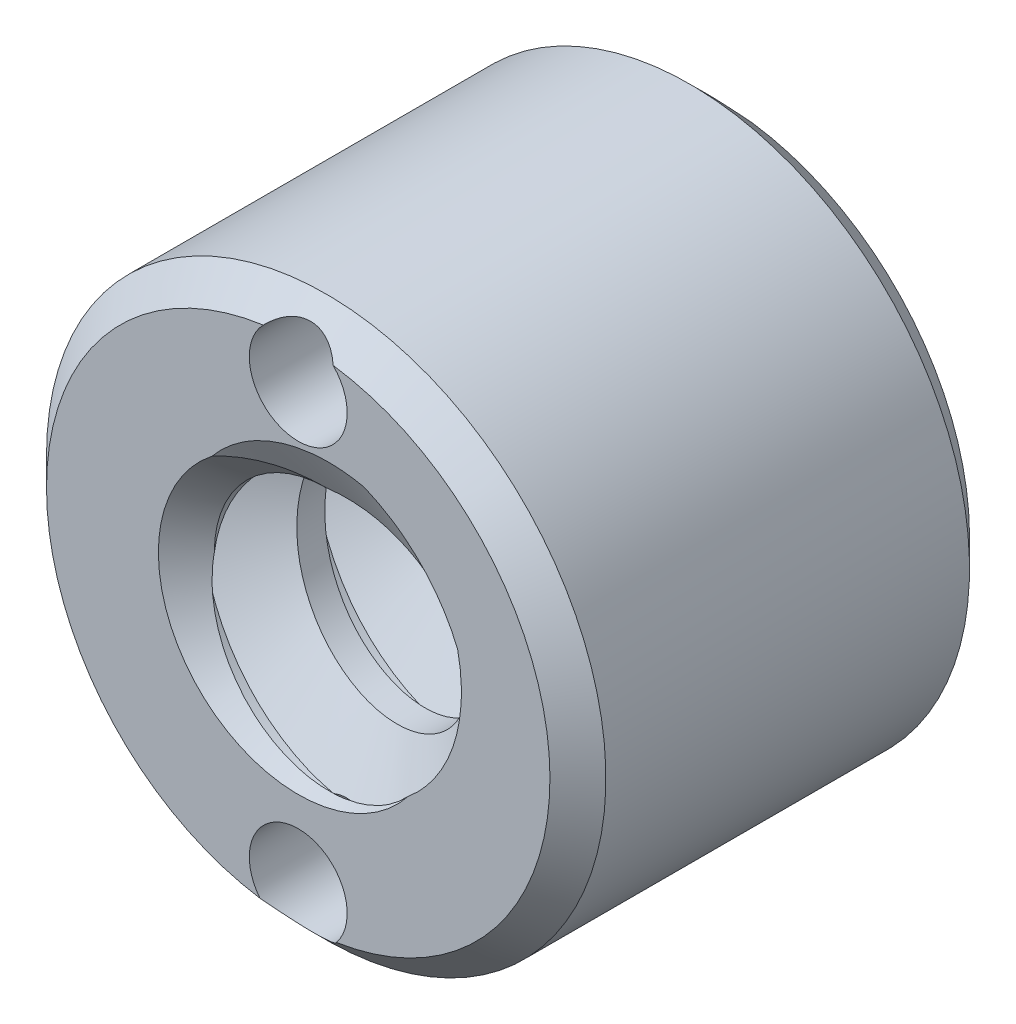
SolidWorks part; units mm, degrees
material "Alliage 1060"
ref_plane "Front Plane" through (0, 0, 0) normal (0, 0, 1) x (1, 0, 0)
ref_plane "Top Plane" through (0, 0, 0) normal (0, 1, 0) x (1, 0, 0)
ref_plane "Right Plane" through (0, 0, 0) normal (1, 0, 0) x (0, 0, -1)
sketch "Sketch1" plane through (0, 0, 0) normal (0, 0, 1) x (1, 0, 0)
  circle A0 centre (0, 0) radius 4
  circle A1 centre (0, 0) radius 10
  circle A2 centre (0, 7.6883) radius 1.75
  circle A3 centre (0, -7.805) radius 1.75
  dimension "D1" = 20
  dimension "D2" = 8
  dimension "D3" = 3.5
extrude "Boss-Extrude1" add sketch "Sketch1" along normal blind 15
chamfer "Chamfer3" distance 1 angle 45 4 edges at (4, 0, 15) (4, 0, 0) (10, 0, 0) (10, 0, 15)
thread "Thread1" pitch 4 method cut profile "Thread Profile1" start angle 0, offset 4, length 0, pitch 4, diameter 8
ref_plane "Plane1" through (-4, 0, 18) normal (0, -1, 0) x (-1, 0, 0)
sketch "Thread Profile1" plane through (-4, 0, 18) normal (0, -1, 0) x (-1, 0, 0)
  line L0 (0, 0) -> (0, 4) construction
  line L1 (0, 0) -> (2.1651, 1.25)
  line L2 (2.1651, 1.25) -> (2.1651, 1.75)
  line L3 (2.1651, 1.75) -> (0, 3)
  line L4 (2.1651, 1.5) -> (0, 1.5) construction
  line L11 (0, 0) -> (0, 3)
  point P2 (0, 0)
  dimension "Pitch" = 4
  dimension "Profile_Angle" = 60
  dimension "Profile_Land" = 0.5
  dimension "Profile_Height" = 2.1651
